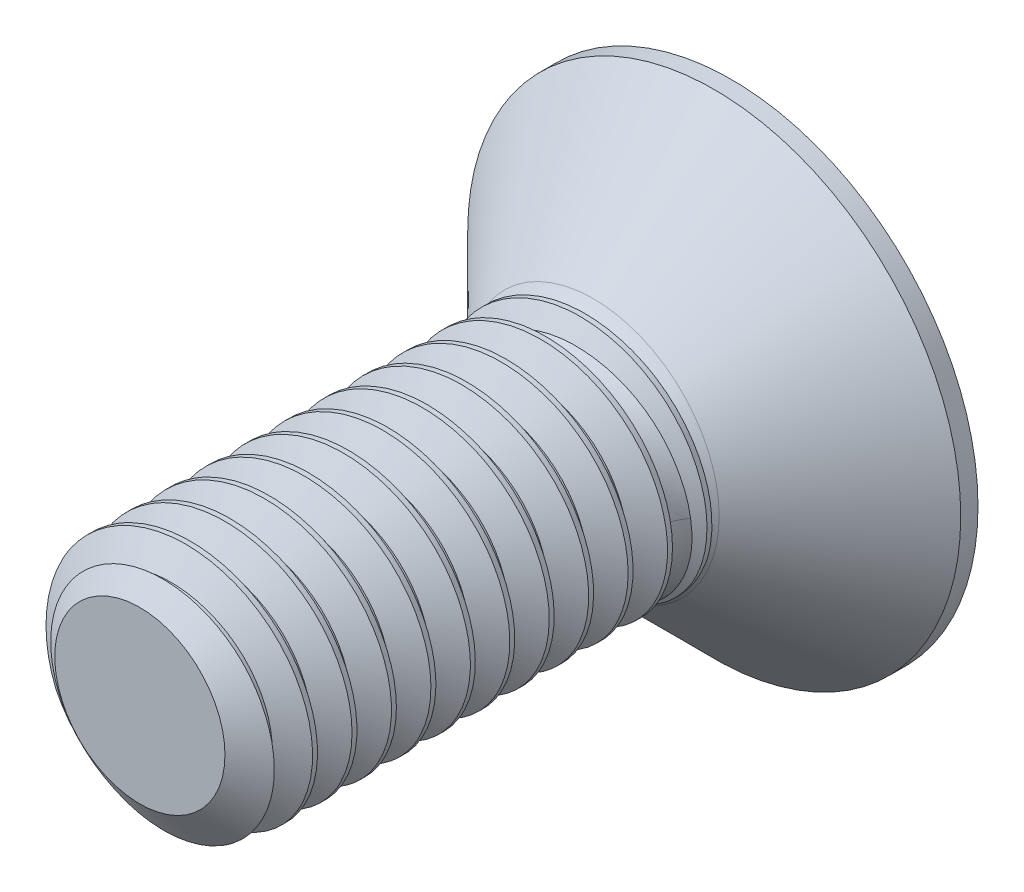
SolidWorks part; units mm, degrees
ref_plane "Front Plane" through (0, 0, 0) normal (0, 0, 1) x (1, 0, 0)
ref_plane "Top Plane" through (0, 0, 0) normal (0, 1, 0) x (1, 0, 0)
ref_plane "Right Plane" through (0, 0, 0) normal (1, 0, 0) x (0, 0, -1)
sketch "Sketch1" plane through (0, 0, 0) normal (0, 0, 1) x (1, 0, 0)
  circle A0 centre (0, 0) radius 2.5
  dimension "OD" = 5
extrude "Extrude1" add sketch "Sketch1" against normal blind 12
sketch "Sketch2" plane through (0, 0, 0) normal (0, 0, 1) x (1, 0, 0)
  circle A0 centre (0, 0) radius 2.5 construction
  circle A1 centre (0, 0) radius 2.5
curve "Helix/Spiral1" pitch 0.8 height 12.8 turns 16 parameters "pitch"=0.8
sketch "Sketch3" plane through (0, 0, 0) normal (1, 0, 0) x (0, 0, -1)
  line L0 (-0.7, 2.5) -> (-0.4, 1.9804)
  line L1 (-0.4, 1.9804) -> (-0.3, 1.9804)
  line L2 (-0.3, 1.9804) -> (0, 2.5)
  line L3 (-0.7, 2.5) -> (0, 2.5)
  line L4 (-0.35, 2.5) -> (-0.35, 1.9804) construction
  line L5 (-0.55, 2.2402) -> (-0.15, 2.2402) construction
  line L6 (0, 2.5) -> (0, -2.5) construction
  dimension "D1" = 0.1
  dimension "D2" = 0.4
  dimension "D3" = 60
sweep "Cut-Sweep1" cut profiles "Sketch3" path "Helix/Spiral1"
sketch "Sketch4" plane through (0, 0, 0) normal (1, 0, 0) x (0, 0, -1)
  line L0 (0.5417, 2.5) -> (0, 1.7264)
  line L1 (0, 1.7264) -> (0, 2.5)
  line L2 (0.5417, 2.5) -> (0, 2.5)
  line L3 (-0.7, 2.5) -> (0, 2.5) construction
  line L4 (0, 0) -> (7.0209, 0) construction
  dimension "D1" = 55
  dimension "D2" = 0.254
revolve "Cut-Revolve1" cut sketch "Sketch4" angle 360 about L4
sketch "Sketch5" plane through (0, 0, 0) normal (1, 0, 0) x (0, 0, -1)
  line L0 (12, -1.991) -> (12, 1.7838) construction
  line L1 (12, 2.55) -> (18.1906, 2.55)
  line L2 (12, 2.55) -> (12, 0)
  line L3 (12, 0) -> (18, 0)
  line L4 (18, 2.2198) -> (18, 0)
  line L5 (18.1906, 2.55) -> (18, 2.2198)
  line L6 (0, 0) -> (9.9695, 0) construction
  point P3 (18, 2.55)
  point P10 (18, 2.55)
  dimension "D1" = 0.3302
  dimension "Thread min" = 18
  dimension "D2" = 0.05
  dimension "D3" = 30
revolve "partially thread" [suppressed] add sketch "Sketch5" angle 360 about L6
sketch "Sketch6" plane through (0, 0, -12) normal (0, 0, -1) x (-1, 0, 0)
  circle A0 centre (0, 0) radius 5
  dimension "head dia" = 10
extrude "Extrude2" add sketch "Sketch6" against normal blind 2.8
sketch "Sketch10" plane through (0, 0, 0) normal (1, 0, 0) x (0, 0, -1)
  line L0 (11.65, -5) -> (9.2, -2.55)
  line L1 (9.2, -2.55) -> (9.2, -5)
  line L2 (11.65, -5) -> (9.2, -5)
  line L3 (0, 0) -> (9.2, 0) construction
  line L4 (9.2, 5) -> (9.2, -5) construction
  line L5 (11.65, 5) -> (9.2, 5) construction
  line L6 (9.2, 2.55) -> (9.2, 5) construction
  line L7 (11.65, 5) -> (9.2, 2.55) construction
  line L8 (9.2, 5) -> (9.2, -5) construction
  line L9 (9.2, 2.55) -> (9.2, -2.55) construction
  dimension "D1" = 45
  dimension "D2" = 0.05
revolve "Cut-Revolve2" cut sketch "Sketch10" angle 360 about L3
sketch "Sketch11" plane through (0, 0, 0) normal (1, 0, 0) x (0, 0, -1)
  line L0 (-0.4, 1.9804) -> (-0.3, 1.9804) construction
  line L1 (11.65, 5) -> (9.2, 2.55) construction
  line L2 (7.8248, 1.9804) -> (7.8248, 0)
  line L3 (7.8248, 0) -> (9.2, 0)
  line L4 (9.2, 2.55) -> (9.2, 0)
  line L5 (0, 0) -> (9.2, 0) construction
  arc A0 (9.2, 2.55) -> (7.8248, 1.9804) centre (7.8248, 3.9252) cw
revolve "Revolve1" add sketch "Sketch11" angle 360 about L3
sketch "Sketch7" plane through (0, 0, -12) normal (0, 0, 1) x (1, 0, 0)
  line L1 (0, 1.7321) -> (-1.5, 0.866)
  line L2 (-1.5, 0.866) -> (-1.5, -0.866)
  line L3 (-1.5, -0.866) -> (0, -1.7321)
  line L4 (0, -1.7321) -> (1.5, -0.866)
  line L5 (1.5, -0.866) -> (1.5, 0.866)
  line L6 (1.5, 0.866) -> (0, 1.7321)
  circle A0 centre (0, 0) radius 1.5 construction
  dimension "hex dia" = 3
extrude "Cut-Extrude1" cut sketch "Sketch7" along normal blind 2.25
sketch "Sketch8" plane through (0, 0, -12) normal (0, 0, 1) x (1, 0, 0)
  circle A0 centre (0, 0) radius 1.7321
extrude "Cut-Extrude2" cut sketch "Sketch8" along normal through all draft 45
equation "\"D3@Helix/Spiral1\" = \"screw length@Extrude1\"+\"pitch@Helix/Spiral1\""
equation "\"D1@Sketch3\" = \"pitch@Helix/Spiral1\"*.125"
equation "\"D2@Sketch3\" = \"pitch@Helix/Spiral1\"*.5"
equation "\"D1@Cut-Extrude1\" = \"hex dia@Sketch7\"*.75"
equation "\"D2@Sketch10\" = \"D2@Sketch5\""
